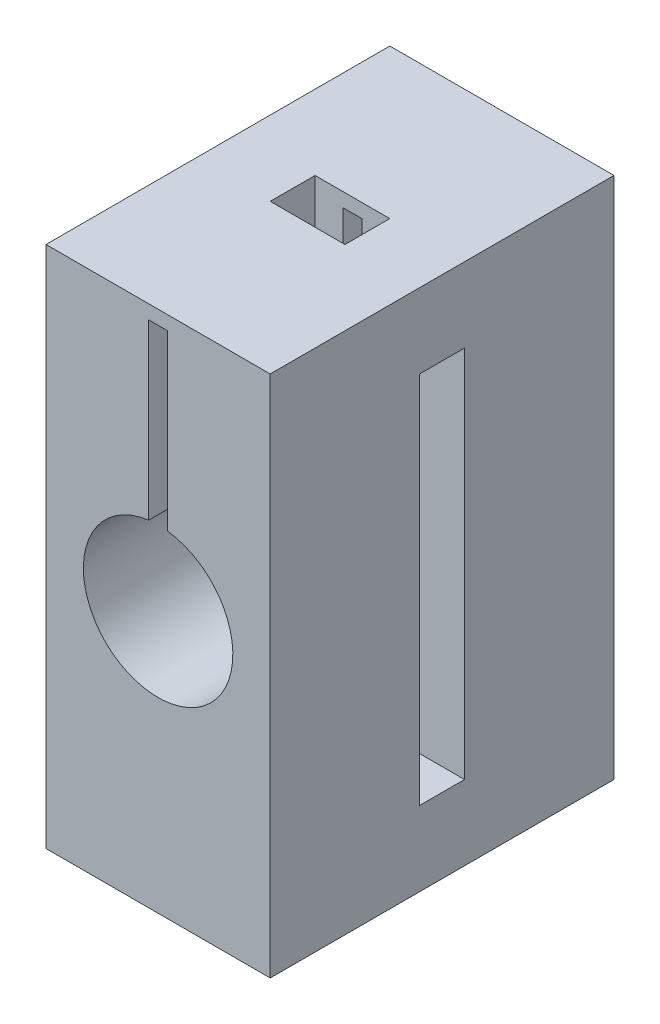
SolidWorks part; units mm, degrees
ref_plane "Front Plane" through (0, 0, 0) normal (0, 0, 1) x (1, 0, 0)
ref_plane "Top Plane" through (0, 0, 0) normal (0, 1, 0) x (1, 0, 0)
ref_plane "Right Plane" through (0, 0, 0) normal (1, 0, 0) x (0, 0, -1)
sketch "Sketch1" plane through (0, 0, 0) normal (0, 0, 1) x (1, 0, 0)
  line L0 (-7.5, -12.5) -> (7.5, -12.5)
  line L1 (7.5, 17.5) -> (-7.5, 17.5)
  line L2 (7.5, 17.5) -> (7.5, -17.5)
  line L3 (7.5, -17.5) -> (-7.5, -17.5)
  line L4 (-7.5, 17.5) -> (-7.5, -17.5)
  line L5 (7.5, 17.5) -> (-7.5, -17.5) construction
  line L6 (7.5, -17.5) -> (-7.5, 17.5) construction
  line L7 (0.6365, 16.5648) -> (-0.6365, 16.5648)
  line L8 (0.6365, 16.5648) -> (0.6365, 3.1387)
  line L9 (0.6365, 3.1387) -> (-0.6365, 3.1387)
  line L10 (-0.6365, 16.5648) -> (-0.6365, 3.1387)
  line L11 (0.6365, 16.5648) -> (-0.6365, 3.1387) construction
  line L12 (0, 0) -> (-5.3234, 0) construction
  line L13 (0.6365, 3.1387) -> (-0.6365, 16.5648) construction
  line L15 (-7.5, 17.5) -> (-2.5, 17.5)
  line L16 (-7.5, 17.5) -> (-7.5, 12.5)
  line L17 (-7.5, 12.5) -> (-2.5, 12.5)
  line L18 (-2.5, 17.5) -> (-2.5, 12.5)
  line L19 (0, -2.44) -> (0, 1.51) construction
  line L20 (7.5, 17.5) -> (2.5, 17.5)
  line L21 (7.5, 17.5) -> (7.5, 12.5)
  line L22 (7.5, 12.5) -> (2.5, 12.5)
  line L23 (2.5, 17.5) -> (2.5, 12.5)
  circle A0 centre (0, 0) radius 1.6
  circle A1 centre (0, 0) radius 2.4
  circle A2 centre (0, 0) radius 11.75 construction
  circle A3 centre (0, 0) radius 5
  point P8 (0, 9.8517)
  dimension "D1" = 4.8
  dimension "D2" = 3.2
  dimension "D4" = 23.5
  dimension "D9" = 10
  dimension "D3" = 15
  dimension "D5" = 1.2729
  dimension "D6" = 5
  dimension "D7" = 35
  dimension "D8" = 5
extrude "Boss-Extrude4" add sketch "Sketch1" along normal blind 10 contours L1 L4 L3 L2 A1 | A1 A0 | L18 L1 L4 L17 | L1 L23 L22 L2 | L0 L4 L3 L2 | L23 L1 L18 L17 L4 L0 L2 L22 A3 L10 L7 L8 region at (-7.1646, 0, 0) region at (0, -15, 0) region at (-5, 15, 0) region at (5, 15, 0) region at (3.6479, 3.2096, 0) region at (-2.3321, 0, 0)
extrude "Cut-Extrude3" cut sketch "Sketch1<9>" along normal blind 8 contours A1 A0 region at (-2.3321, 0, 0)
sketch "Sketch1<9>" plane through (0, 0, 0) normal (0, 0, 1) x (1, 0, 0) same geometry as "Sketch1"
extrude "Boss-Extrude5" add sketch "Sketch1<10>" along normal blind 13 contours L0 L4 L3 L2 | L18 L1 L4 L17 | L1 L23 L22 L2 region at (0, -15, 0) region at (-5, 15, 0) region at (5, 15, 0)
sketch "Sketch1<10>" plane through (0, 0, 0) normal (0, 0, 1) x (1, 0, 0) same geometry as "Sketch1"
extrude "Boss-Extrude6" add sketch "Sketch1<11>" along normal blind 10 from offset 13 contours L23 L1 L18 L17 L4 L0 L2 L22 A3 L10 L7 L8 | L18 L1 L4 L17 | L1 L23 L22 L2 | L0 L4 L3 L2 region at (-7.1646, 0, 0) region at (0, -15, 0) region at (-5, 15, 0) region at (5, 15, 0)
sketch "Sketch1<11>" plane through (0, 0, 0) normal (0, 0, 1) x (1, 0, 0) same geometry as "Sketch1"
